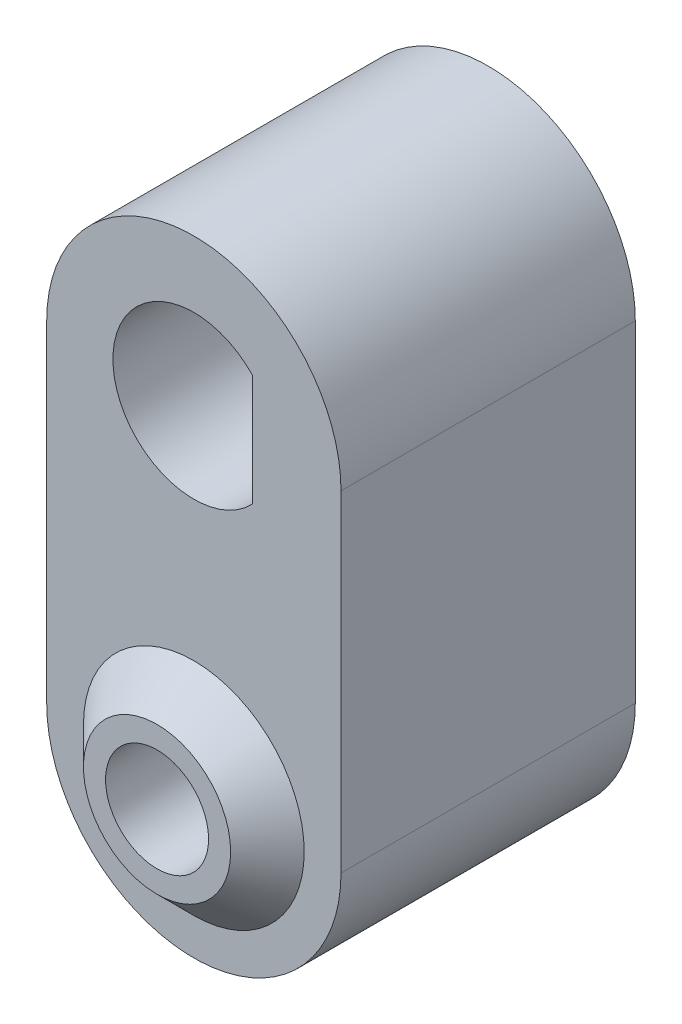
SolidWorks part; units mm, degrees
ref_plane "前视基准面" through (0, 0, 0) normal (0, 0, 1) x (1, 0, 0)
ref_plane "上视基准面" through (0, 0, 0) normal (0, 1, 0) x (1, 0, 0)
ref_plane "右视基准面" through (0, 0, 0) normal (1, 0, 0) x (0, 0, -1)
sketch "草图1" plane through (0, 0, 0) normal (0, 0, 1) x (1, 0, 0)
  line L0 (1.6, 1.51) -> (1.6, -1.51)
  line L12 (3.3486, -9) -> (1.6743, -6.1)
  line L13 (1.6743, -6.1) -> (-1.6743, -6.1)
  line L14 (-1.6743, -6.1) -> (-3.3486, -9)
  line L15 (-3.3486, -9) -> (-1.6743, -11.9)
  line L16 (-1.6743, -11.9) -> (1.6743, -11.9)
  line L17 (1.6743, -11.9) -> (3.3486, -9)
  line L20 (0, 0) -> (0, -9) construction
  line L21 (4, 0) -> (4, -9)
  line L22 (-4, 0) -> (-4, -9)
  circle A1 centre (0, 0) radius 2.2
  circle A16 centre (0, -9) radius 1.4
  circle A18 centre (0, -9) radius 2.9 construction
  arc A21 (4, 0) -> (-4, 0) centre (0, 0) ccw
  arc A22 (-4, -9) -> (4, -9) centre (0, -9) ccw
  circle A24 centre (0, -9) radius 2
  point P24 (0, 0)
  point P29 (0, -4.5)
  dimension "D1" = 4.4
  dimension "D3" = 4
  dimension "D4" = 2.8
  dimension "D5" = 9
  dimension "D2" = 1.6
extrude "凸台-拉伸2" add sketch "草图1" along normal blind 8 contours L22 A22 L21 A21
extrude "切除-拉伸2" cut sketch "草图1<6>" along normal blind 8 contours L0 A1 | A16 region at (-0.1644, 0, 0)
sketch "草图1<6>" plane through (0, 0, 0) normal (0, 0, 1) x (1, 0, 0) same geometry as "草图1"
extrude "凸台-拉伸3" add sketch "草图1<8>" along normal blind 9 contours A24 A16 region at (-1.9434, -9, 0)
sketch "草图1<8>" plane through (0, 0, 0) normal (0, 0, 1) x (1, 0, 0) same geometry as "草图1"
chamfer "倒角2" distance 1 angle 45 1 edges at (2, -9, 8)
